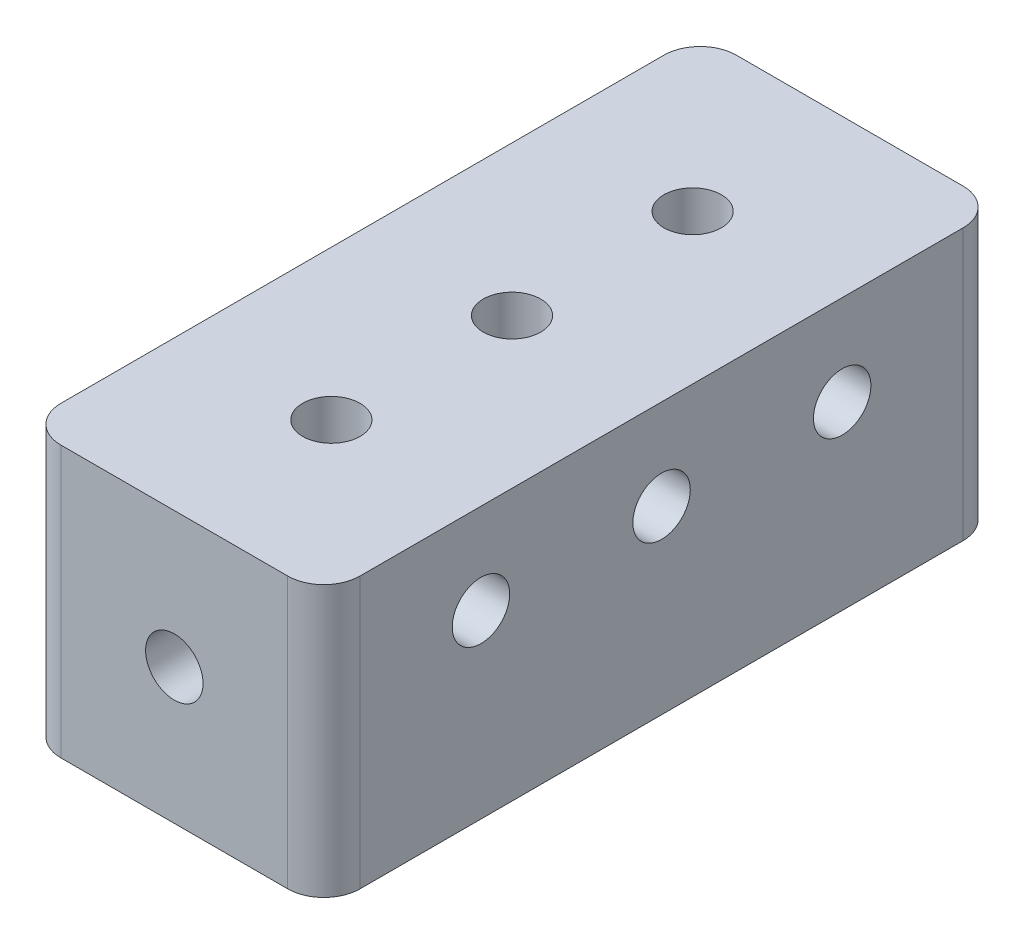
SolidWorks part; units mm, degrees
ref_plane "Front Plane" through (0, 0, 0) normal (0, 0, 1) x (1, 0, 0)
ref_plane "Top Plane" through (0, 0, 0) normal (0, 1, 0) x (1, 0, 0)
ref_plane "Right Plane" through (0, 0, 0) normal (1, 0, 0) x (0, 0, -1)
sketch "Sketch1" plane through (0, 0, 0) normal (0, 1, 0) x (1, 0, 0)
  line L1 (-10.5156, -23.7427) -> (10.5156, -23.7427)
  line L2 (-10.5156, -23.7427) -> (-10.5156, 23.7426)
  line L3 (-10.5156, 23.7426) -> (10.5156, 23.7426)
  line L4 (10.5156, -23.7427) -> (10.5156, 23.7426)
  line L5 (-10.5156, -23.7427) -> (10.5156, 23.7426) construction
  line L6 (-10.5156, 23.7426) -> (10.5156, -23.7427) construction
  point P0 (0, 0)
  dimension "D1" = 21.0312
  dimension "D2" = 47.4853
extrude "Boss-Extrude1" add sketch "Sketch1" along normal mid plane 19.05
sketch "Sketch2" plane through (0, 0, 23.7427) normal (0, 0, 1) x (1, 0, 0)
  circle A0 centre (0, 0) radius 2.0193
  point P2 (0, 0)
  point P5 (0, 0)
  point P6 (0, 0)
  point P8 (0, 0)
  dimension "D3" = 4.0386
extrude "Cut-Extrude1" cut sketch "Sketch2" against normal blind 9.525
sketch "Sketch3" plane through (0, 0, -23.7426) normal (0, 0, -1) x (-1, 0, 0)
  circle A0 centre (0, 0) radius 2.0193 construction
  circle A1 centre (0, 0) radius 2.0193
extrude "Cut-Extrude2" cut sketch "Sketch3" against normal blind 9.525
sketch "Sketch4" plane through (10.5156, 0, 0) normal (1, 0, 0) x (0, 0, -1)
  line L0 (-23.7427, 9.525) -> (23.7426, 9.525) construction
  circle A0 centre (-12.7, 3.175) radius 2.0193
  circle A1 centre (12.7, 3.175) radius 2.0193
  circle A2 centre (0, 3.175) radius 2.0193
  point P4 (0, 0)
  point P11 (0, 0)
  dimension "D5" = 4.0386
  dimension "D1" = 6.35
  dimension "D3" = 12.7
  dimension "D4" = 12.7
extrude "Cut-Extrude3" cut sketch "Sketch4" against normal blind 6.35
sketch "Sketch5" plane through (-10.5156, 0, 0) normal (-1, 0, 0) x (0, 0, 1)
  circle A0 centre (-12.7, 3.175) radius 2.0193 construction
  circle A1 centre (0, 3.175) radius 2.0193 construction
  circle A2 centre (12.7, 3.175) radius 2.0193 construction
  circle A3 centre (-12.7, 3.175) radius 2.0193
  circle A4 centre (0, 3.175) radius 2.0193
  circle A5 centre (12.7, 3.175) radius 2.0193
extrude "Cut-Extrude4" cut sketch "Sketch5" against normal blind 6.35
sketch "Sketch6" plane through (0, 9.525, 0) normal (0, 1, 0) x (1, 0, 0)
  line L1 (-10.5156, 23.7426) -> (-10.5156, -23.7427) construction
  circle A0 centre (0, 12.7) radius 2.0193
  circle A1 centre (0, 0) radius 2.0193
  circle A2 centre (0, -12.7) radius 2.0193
  point P6 (0, 0)
  point P7 (0, 0)
  point P8 (0.6022, 5.4803)
  point P14 (0, 0)
  dimension "D1" = 4.0386
  dimension "D6" = 10.5156
  dimension "D2" = 12.7
  dimension "D3" = 12.7
extrude "Cut-Extrude5" cut sketch "Sketch6" against normal blind 6.35
fillet "Fillet1" radius 2.54 4 edges at (10.5156, 0, 23.7427) (-10.5156, 0, 23.7427) (-10.5156, 0, -23.7426) (10.5156, 0, -23.7426)
